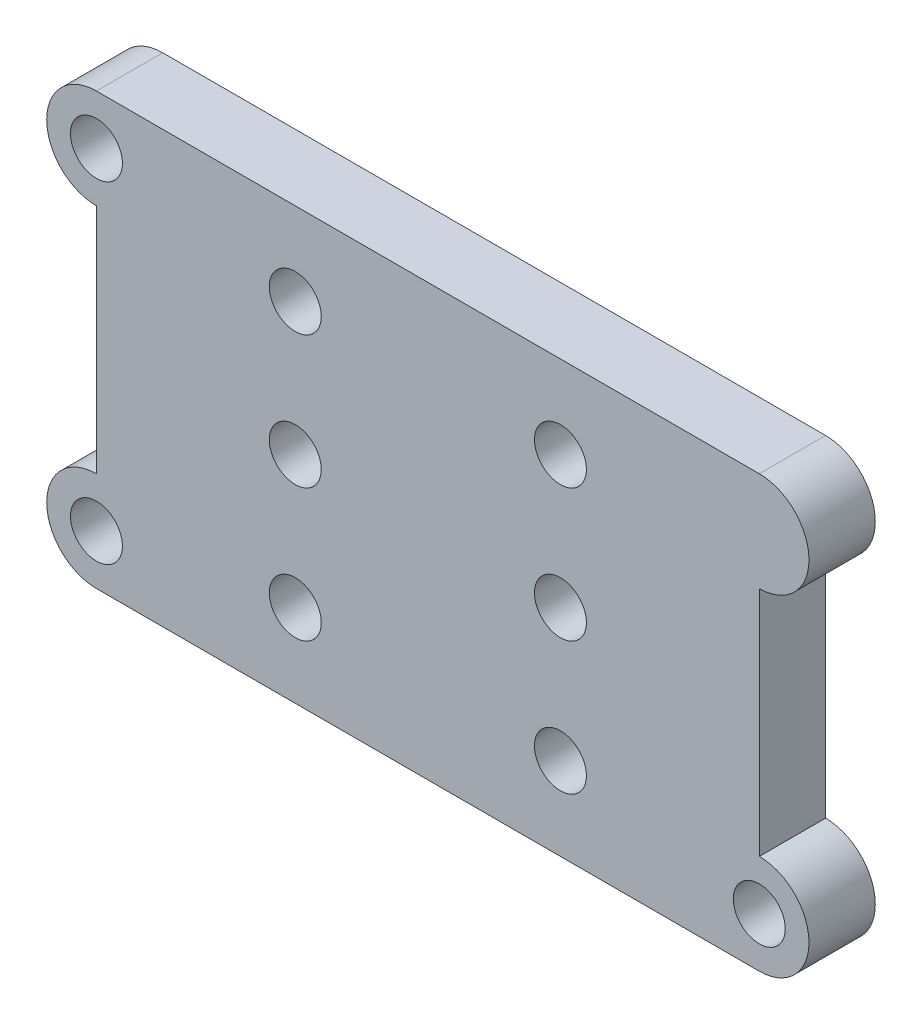
SolidWorks part; units mm, degrees
material "6061-T6 (SS)"
ref_plane "Front Plane" through (0, 0, 0) normal (0, 0, 1) x (1, 0, 0)
ref_plane "Top Plane" through (0, 0, 0) normal (0, 1, 0) x (1, 0, 0)
ref_plane "Right Plane" through (0, 0, 0) normal (1, 0, 0) x (0, 0, -1)
sketch "Sketch1" plane through (0, 0, 0) normal (0, 0, 1) x (1, 0, 0)
  line L0 (0, 36.5125) -> (63.5, 36.5125) construction
  line L5 (0, 4.7625) -> (63.5, 4.7625) construction
  line L6 (63.5, 31.75) -> (63.5, 9.525)
  line L7 (0, 36.5125) -> (63.5, 4.7625) construction
  line L8 (0, 4.7625) -> (63.5, 36.5125) construction
  line L10 (0, 41.275) -> (63.5, 41.275)
  line L11 (63.5, 0) -> (0, 0)
  line L12 (0, 31.75) -> (0, 9.525)
  circle A0 centre (63.5, 36.5125) radius 2.4892
  circle A1 centre (0, 36.5125) radius 2.4892
  circle A2 centre (0, 4.7625) radius 2.4892
  circle A3 centre (63.5, 4.7625) radius 2.4892
  circle A4 centre (0, 36.5125) radius 4.7625
  circle A5 centre (63.5, 36.5125) radius 4.7625
  circle A6 centre (63.5, 4.7625) radius 4.7625
  circle A7 centre (0, 4.7625) radius 4.7625
  circle A8 centre (19.05, 7.9375) radius 2.4892
  circle A14 centre (44.45, 7.9375) radius 2.4892
  circle A15 centre (44.45, 20.6375) radius 2.4892
  circle A16 centre (44.45, 33.3375) radius 2.4892
  circle A17 centre (19.05, 20.6375) radius 2.4892
  circle A18 centre (19.05, 33.3375) radius 2.4892
  point P0 (31.75, 20.6375)
  point P5 (19.05, 7.9375)
  point P15 (44.45, 9.525)
  point P19 (0, 0)
  point P37 (31.75, 20.6375)
  point P38 (19.05, 33.3375)
  point P39 (17.3997, 20.6375)
  point P40 (44.45, 20.6375)
  point P41 (44.45, 7.9375)
  point P42 (44.45, 33.3375)
  point P43 (44.45, 20.6375)
  point P44 (44.45, 33.3375)
  point P45 (44.45, 20.6375)
  point P46 (41.6863, 7.9375)
  point P47 (0, 0)
  dimension "D3" = 4.9784
  dimension "D4" = 9.525
  dimension "D6" = 3
  dimension "D9" = 4.9784
  dimension "D1" = 63.5
  dimension "D2" = 31.75
  dimension "D5" = 2
  dimension "D7" = 12.7
  dimension "D8" = 25.4
  dimension "D10" = 12.7
extrude "Boss-Extrude1" add sketch "Sketch1" along normal blind 6.35 contours A7 L11 A6 L6 A5 L10 A4 L12 A18 A17 A16 A15 A14 A8 | A4 A1 | A7 A2 | A6 A3 | A5 A0 | A0 region at (31.75, 20.6375, 0) region at (58.8722, 36.5125, 0) region at (66.7723, 8.0348, 0) region at (3.2723, 39.7848, 0) region at (-4.6278, 4.7625, 0)
